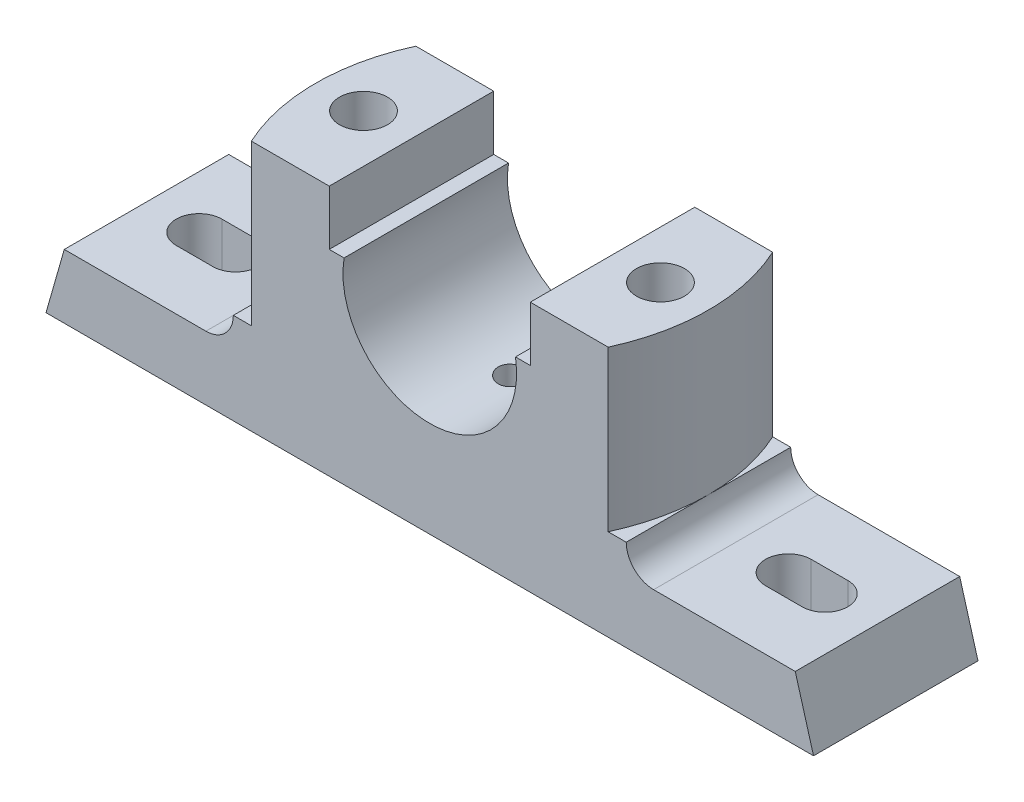
SolidWorks part; units mm, degrees
ref_plane "Front Plane" through (0, 0, 0) normal (0, 0, 1) x (1, 0, 0)
ref_plane "Top Plane" through (0, 0, 0) normal (0, 1, 0) x (1, 0, 0)
ref_plane "Right Plane" through (0, 0, 0) normal (1, 0, 0) x (0, 0, -1)
sketch "Sketch1" plane through (0, 0, 0) normal (0, 0, 1) x (1, 0, 0)
  line L1 (-45.7921, 63.3116) -> (122.2079, 63.3116)
  line L2 (-45.7921, 63.3116) -> (-45.7921, 8.3116)
  line L3 (-45.7921, 8.3116) -> (122.2079, 8.3116)
  line L4 (122.2079, 63.3116) -> (122.2079, 8.3116)
extrude "Boss-Extrude2" add sketch "Sketch1" against normal blind 36
sketch "Sketch3" plane through (0, 63.3116, 0) normal (0, 1, 0) x (1, 0, 0)
  line L0 (81.2079, 36) -> (81.2079, 0)
  line L1 (122.2079, 36) -> (-45.7921, 36) construction
  line L2 (122.2079, 0) -> (-45.7921, 0) construction
  line L3 (-4.7921, 36) -> (-4.7921, 0)
  line L4 (-4.7921, 36) -> (-0.8433, 36)
  line L5 (-4.7921, 0) -> (-0.8433, 0)
  line L6 (77.2592, 36) -> (81.2079, 36)
  line L7 (77.2592, 0) -> (81.2079, 0)
  line L12 (-45.7921, 0) -> (122.2079, 0)
  line L13 (122.2079, 0) -> (122.2079, 36)
  line L14 (122.2079, 36) -> (-45.7921, 36)
  line L15 (-45.7921, 36) -> (-45.7921, 0)
  line L16 (-45.7921, 0) -> (122.2079, 0)
  line L17 (122.2079, 0) -> (122.2079, 36)
  line L18 (122.2079, 36) -> (-45.7921, 36)
  line L19 (-45.7921, 36) -> (-45.7921, 0)
  arc A0 (-0.8433, 36) -> (-0.8433, 0) centre (38.2079, 18) ccw
  arc A1 (77.2592, 0) -> (77.2592, 36) centre (38.2079, 18) ccw
  line M6 (-45.7921, 0) -> (122.2079, 0)
  line M7 (122.2079, 0) -> (122.2079, 36)
  line M8 (122.2079, 36) -> (-45.7921, 36)
  line M9 (-45.7921, 36) -> (-45.7921, 0)
  dimension "D1" = 0
extrude "Cut-Extrude2" cut sketch "Sketch3" against normal blind 41 contours L0 M8 M6 M7 | L3 M8 M9 M6 region at (101.7079, 63.3116, -18) region at (-25.2921, 63.3116, -18)
sketch "Sketch4" plane through (0, 63.3116, 0) normal (0, 1, 0) x (1, 0, 0)
  line L0 (-4.7921, 36) -> (-4.7921, 0)
  line L1 (-4.7921, 36) -> (-4.7921, 0) construction
  line L2 (-4.7921, 36) -> (-4.7921, 0) construction
  line L3 (-0.8433, 0) -> (-4.7921, 0)
  line L4 (-0.8433, 36) -> (-4.7921, 36)
  line L5 (77.2592, 36) -> (81.2079, 36)
  line L6 (81.2079, 36) -> (-4.7921, 36) construction
  line L7 (81.2079, 36) -> (81.2079, 0)
  line L8 (77.2592, 0) -> (81.2079, 0)
  line L9 (81.2079, 0) -> (-4.7921, 0) construction
  circle A0 centre (38.2079, 18) radius 43
  line M2 (81.2079, 0) -> (81.2079, 36)
  line M3 (81.2079, 36) -> (-4.7921, 36)
  line M4 (-4.7921, 36) -> (-4.7921, 0)
  line M5 (-4.7921, 0) -> (81.2079, 0)
extrude "Cut-Extrude4" cut sketch "Sketch4" against normal blind 35 contours A0 M3 M4 | A0 L0 M5 | A0 L7 M3 | A0 M5 M2 region at (-3.6174, 63.3116, -31.5424) region at (-3.6174, 63.3116, -4.4576) region at (80.0332, 63.3116, -31.5424) region at (80.0332, 63.3116, -4.4576)
sketch "Sketch5" plane through (0, 63.3116, 0) normal (0, 1, 0) x (1, 0, 0)
  line L0 (77.2592, 36) -> (-0.8433, 36) construction
  line L1 (16.2079, 0) -> (60.2079, 0)
  line L2 (16.2079, 0) -> (16.2079, 36)
  line L3 (16.2079, 36) -> (60.2079, 36)
  line L4 (60.2079, 0) -> (60.2079, 36)
  line L5 (16.2079, 0) -> (60.2079, 36) construction
  line L6 (16.2079, 36) -> (60.2079, 0) construction
  point P0 (38.2079, 18)
extrude "Cut-Extrude5" cut sketch "Sketch5" against normal blind 12
sketch "Sketch8" plane through (0, 0, 0) normal (0, 0, 1) x (1, 0, 0)
  line L0 (16.2079, 51.3116) -> (16.2079, 48.3116)
  circle A0 centre (38.2079, 48.3116) radius 19
  line M2 (60.2079, 51.3116) -> (16.2079, 51.3116)
extrude "Cut-Extrude6" cut sketch "Sketch8" against normal blind 42 contours A0 M2 region at (38.2079, 41.8425, 0)
ref_plane "Plane1" through (0, 63.3116, 0) normal (0, 1, 0) x (1, 0, 0)
sketch "Sketch11" plane through (0, 63.3116, 0) normal (0, 1, 0) x (1, 0, 0)
  line L0 (-4.7921, 36) -> (16.2079, 36)
  circle A0 centre (5.7079, 18) radius 5.25
  circle A1 centre (70.7079, 18) radius 5.25
  point P10 (38.2079, 18)
extrude "Cut-Extrude8" cut sketch "Sketch11" against normal blind 53 contours A0 | A1
sketch "Sketch13" plane through (0, 0, 0) normal (0, 0, 1) x (1, 0, 0)
  line L0 (-45.7921, 22.3116) -> (-45.7921, 8.3116)
  line L1 (-45.7921, 22.3116) -> (-41.7921, 22.3116)
  line L2 (-45.7921, 22.3116) -> (-4.7921, 22.3116) construction
  line L3 (-41.7921, 22.3116) -> (-45.7921, 8.3116)
  line L5 (122.2079, 22.3116) -> (118.2079, 22.3116)
  line L6 (122.2079, 22.3116) -> (122.2079, 8.3116)
  line L7 (118.2079, 22.3116) -> (122.2079, 8.3116)
extrude "Cut-Extrude9" cut sketch "Sketch13" against normal blind 46 contours L3 L0 L1 | L5 L7 L6
fillet "Fillet1" radius 6 2 edges at (81.2079, 22.3116, -18) (-4.7921, 22.3116, -18)
sketch "Sketch15" plane through (0, 22.3116, 0) normal (0, 1, 0) x (1, 0, 0)
  line L14 (-30.2921, 18) -> (-22.2921, 18) construction
  line L15 (-30.2921, 23) -> (-22.2921, 23)
  line L16 (-30.2921, 13) -> (-22.2921, 13)
  line L18 (98.7079, 18) -> (106.7079, 18) construction
  line L19 (98.7079, 23) -> (106.7079, 23)
  line L20 (98.7079, 13) -> (106.7079, 13)
  arc A2 (-30.2921, 23) -> (-30.2921, 13) centre (-30.2921, 18) ccw
  arc A3 (-22.2921, 13) -> (-22.2921, 23) centre (-22.2921, 18) ccw
  arc A4 (98.7079, 23) -> (98.7079, 13) centre (98.7079, 18) ccw
  arc A5 (106.7079, 13) -> (106.7079, 23) centre (106.7079, 18) ccw
  point P10 (-26.2921, 18)
  point P24 (102.7079, 18)
sketch "Sketch25" plane through (0, 0, 0) normal (0, 0, 1) x (1, 0, 0)
  line L2 (16.2079, 51.3116) -> (19.4462, 51.3116) construction
  line L3 (19.2079, 51.3116) -> (19.4462, 51.3116)
  line L5 (19.2079, 51.3116) -> (19.2079, 48.3116)
  line L20 (-10.7921, 22.3116) -> (-41.7921, 22.3116)
  line L21 (-41.7921, 22.3116) -> (-45.7921, 8.3116)
  line L22 (-45.7921, 8.3116) -> (122.2079, 8.3116)
  line L23 (122.2079, 8.3116) -> (118.2079, 22.3116)
  line L24 (118.2079, 22.3116) -> (87.2079, 22.3116)
  line L25 (81.2079, 28.3116) -> (77.2592, 28.3116)
  line L26 (77.2592, 28.3116) -> (77.2592, 63.3116)
  line L27 (77.2592, 63.3116) -> (60.2079, 63.3116)
  line L28 (60.2079, 63.3116) -> (60.2079, 51.3116)
  line L29 (60.2079, 51.3116) -> (56.9696, 51.3116)
  line L30 (19.4462, 51.3116) -> (16.2079, 51.3116)
  line L31 (16.2079, 51.3116) -> (16.2079, 63.3116)
  line L32 (16.2079, 63.3116) -> (-0.8433, 63.3116)
  line L33 (-0.8433, 63.3116) -> (-0.8433, 28.3116)
  line L34 (-0.8433, 28.3116) -> (-4.7921, 28.3116)
  line L35 (-10.7921, 22.3116) -> (-41.7921, 22.3116)
  line L36 (-41.7921, 22.3116) -> (-45.7921, 8.3116)
  line L37 (-45.7921, 8.3116) -> (122.2079, 8.3116)
  line L38 (122.2079, 8.3116) -> (118.2079, 22.3116)
  line L39 (118.2079, 22.3116) -> (87.2079, 22.3116)
  line L40 (81.2079, 28.3116) -> (77.2592, 28.3116)
  line L41 (77.2592, 28.3116) -> (77.2592, 63.3116)
  line L42 (77.2592, 63.3116) -> (60.2079, 63.3116)
  line L43 (60.2079, 63.3116) -> (60.2079, 51.3116)
  line L44 (60.2079, 51.3116) -> (56.9696, 51.3116)
  line L45 (19.4462, 51.3116) -> (16.2079, 51.3116)
  line L46 (16.2079, 51.3116) -> (16.2079, 63.3116)
  line L47 (16.2079, 63.3116) -> (-0.8433, 63.3116)
  line L48 (-0.8433, 63.3116) -> (-0.8433, 28.3116)
  line L49 (-0.8433, 28.3116) -> (-4.7921, 28.3116)
  arc A0 (19.4462, 51.3116) -> (56.9696, 51.3116) centre (38.2079, 48.3116) ccw construction
  arc A4 (81.2079, 28.3116) -> (87.2079, 22.3116) centre (87.2079, 28.3116) ccw
  arc A5 (19.4462, 51.3116) -> (56.9696, 51.3116) centre (38.2079, 48.3116) ccw
  arc A6 (-10.7921, 22.3116) -> (-4.7921, 28.3116) centre (-10.7921, 28.3116) ccw
  arc A7 (81.2079, 28.3116) -> (87.2079, 22.3116) centre (87.2079, 28.3116) ccw
  arc A8 (19.2079, 48.3116) -> (56.9696, 51.3116) centre (38.2079, 48.3116) ccw
  arc A9 (-10.7921, 22.3116) -> (-4.7921, 28.3116) centre (-10.7921, 28.3116) ccw
  dimension "D1" = 0
sketch "Sketch30" plane through (0, 8.3116, 0) normal (0, -1, 0) x (1, 0, 0)
  line L0 (-45.7921, -36) -> (-45.7921, 0) construction
  line L1 (-37.7921, -8) -> (30.2079, -8)
  line L2 (-37.7921, -8) -> (-37.7921, -28)
  line L3 (-37.7921, -28) -> (30.2079, -28)
  line L4 (30.2079, -8) -> (30.2079, -28)
  line L5 (-45.7921, -36) -> (122.2079, -36) construction
  line L6 (122.2079, -36) -> (122.2079, 0) construction
  line L7 (46.2079, -8) -> (114.2079, -8)
  line L8 (46.2079, -8) -> (46.2079, -28)
  line L9 (46.2079, -28) -> (114.2079, -28)
  line L10 (114.2079, -8) -> (114.2079, -28)
  dimension "D1" = 8
  dimension "D2" = 8
  dimension "D3" = 8
  dimension "D4" = 8
extrude "Cut-Extrude14" cut sketch "Sketch30" against normal blind 2
ref_plane "Plane2" through (0, 29, 0) normal (0, 1, 0) x (1, 0, 0)
sketch "Sketch31" plane through (0, 29, 0) normal (0, 1, 0) x (1, 0, 0)
  circle A0 centre (38.2079, 18) radius 3
extrude "Cut-Extrude16" cut sketch "Sketch31" against normal blind 6 and the other way blind 6
sketch "Sketch32" plane through (0, 10.3116, 0) normal (0, -1, 0) x (1, 0, 0)
  line L0 (30.2079, -8) -> (-37.7921, -8) construction
  line L1 (-3.7921, -8) -> (16.2079, -8)
  line L2 (-3.7921, -8) -> (-3.7921, -28)
  line L3 (-3.7921, -28) -> (16.2079, -28)
  line L4 (16.2079, -8) -> (16.2079, -28)
  line L5 (-37.7921, -28) -> (30.2079, -28) construction
  line L6 (114.2079, -8) -> (46.2079, -8) construction
  line L7 (61.0788, -8) -> (81.0788, -8)
  line L8 (61.0788, -8) -> (61.0788, -28)
  line L9 (61.0788, -28) -> (81.0788, -28)
  line L10 (81.0788, -8) -> (81.0788, -28)
  line L11 (46.2079, -28) -> (114.2079, -28) construction
extrude "Cut-Extrude19" cut sketch "Sketch32" against normal blind 7
sketch "Sketch36" plane through (0, 22.3116, 0) normal (0, 1, 0) x (1, 0, 0)
  line L0 (-10.7921, 0) -> (-10.7921, 36) construction
  line L1 (87.2079, 36) -> (87.2079, 0) construction
  point P1 (-10.7921, 18)
  point P2 (87.2079, 18)
  point P6 (102.7079, 18)
  dimension "D1" = 15.5
  dimension "D2" = 15.5
extrude "Cut-Extrude21" cut sketch "Sketch15" against normal blind 12
